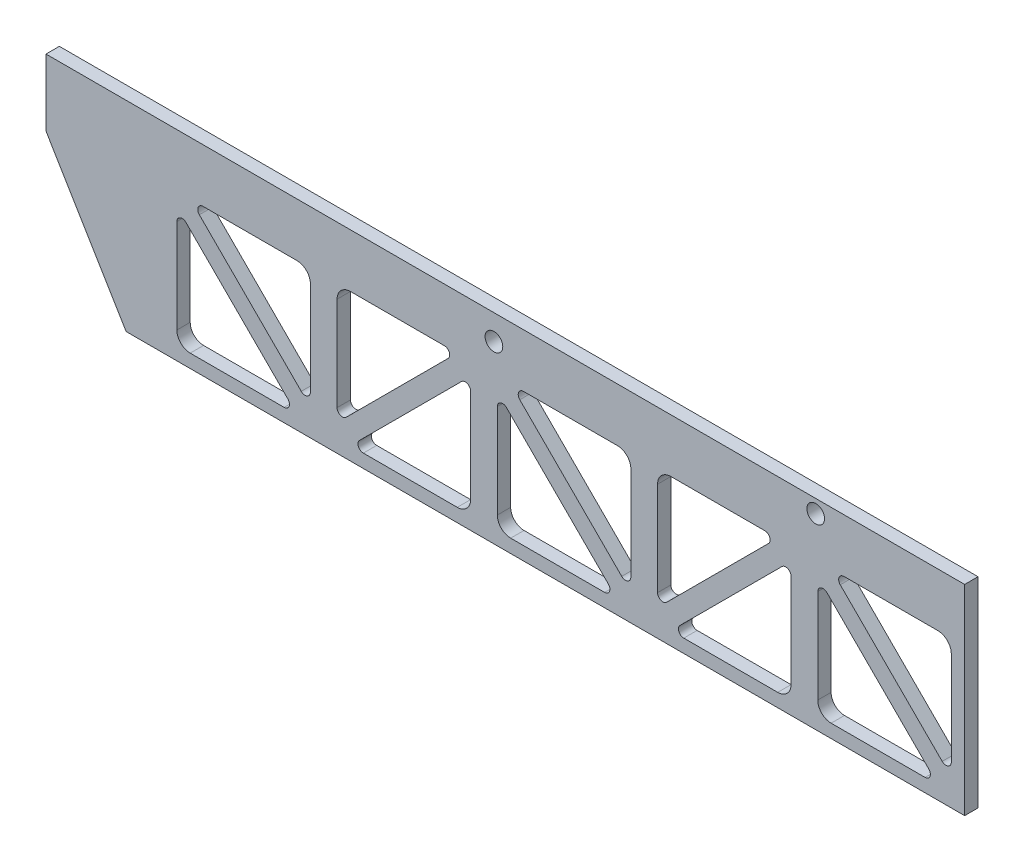
SolidWorks part; units mm, degrees
material "Balsa"
ref_plane "Front Plane" through (0, 0, 0) normal (0, 0, 1) x (1, 0, 0)
ref_plane "Top Plane" through (0, 0, 0) normal (0, 1, 0) x (1, 0, 0)
ref_plane "Right Plane" through (0, 0, 0) normal (1, 0, 0) x (0, 0, -1)
sketch "Model" plane through (0, 0, 0) normal (0, 0, 1) x (1, 0, 0)
  line L0 (-74.8917, 84.8995) -> (-66.8907, 84.8995)
  line L1 (-74.8917, 92.9005) -> (-74.8917, 84.8995)
  line L2 (-66.8907, 92.9005) -> (-74.8917, 92.9005)
  line L3 (-66.8907, 84.8995) -> (-66.8907, 92.9005)
  line L4 (-227.7984, 79.375) -> (-219.7978, 79.375)
  line L5 (-227.7984, 87.3756) -> (-227.7984, 79.375)
  line L6 (-219.7978, 87.3756) -> (-227.7984, 87.3756)
  line L7 (-219.7978, 79.375) -> (-219.7978, 87.3756)
  line L8 (-171.2321, 6.35) -> (-215.9, 6.35)
  line L9 (-222.25, 57.3679) -> (-222.25, 12.7)
  line L10 (-217.9139, 59.1639) -> (-169.4361, 10.6861)
  line L11 (-234.95, 57.3679) -> (-234.95, 12.7)
  line L12 (-241.3, 6.35) -> (-285.9679, 6.35)
  line L13 (-239.2861, 59.1639) -> (-287.7639, 10.6861)
  line L14 (-294.1139, 17.0361) -> (-245.6361, 65.5139)
  line L15 (-298.45, 63.5) -> (-298.45, 18.8321)
  line L16 (-247.4321, 69.85) -> (-292.1, 69.85)
  line L17 (-323.6321, 6.35) -> (-368.3, 6.35)
  line L18 (-374.65, 57.3679) -> (-374.65, 12.7)
  line L19 (-370.3139, 59.1639) -> (-321.8361, 10.6861)
  line L20 (-18.8321, 6.35) -> (-63.5, 6.35)
  line L21 (-69.85, 57.3679) -> (-69.85, 12.7)
  line L22 (-17.0361, 10.6861) -> (-65.5139, 59.1639)
  line L23 (-82.55, 57.3679) -> (-82.55, 12.7)
  line L24 (-88.9, 6.35) -> (-133.5679, 6.35)
  line L25 (-86.8861, 59.1639) -> (-135.3639, 10.6861)
  line L26 (-93.2361, 65.5139) -> (-141.7139, 17.0361)
  line L27 (-146.05, 63.5) -> (-146.05, 18.8321)
  line L28 (-95.0321, 69.85) -> (-139.7, 69.85)
  line L29 (-163.0861, 17.0361) -> (-211.5639, 65.5139)
  line L30 (-165.1, 69.85) -> (-209.7679, 69.85)
  line L31 (-158.75, 63.5) -> (-158.75, 18.8321)
  line L32 (-315.4861, 17.0361) -> (-363.9639, 65.5139)
  line L33 (-317.5, 69.85) -> (-362.1679, 69.85)
  line L34 (-311.15, 63.5) -> (-311.15, 18.8321)
  line L35 (-398.78, 0) -> (-436.88, 63.5)
  line L36 (0, 0) -> (-398.78, 0)
  line L37 (0, 0) -> (0, 95.25)
  line L38 (0, 95.25) -> (-436.88, 95.25)
  line L39 (-436.88, 63.5) -> (-436.88, 95.25)
  line L40 (-6.35, 63.5) -> (-6.35, 18.8321)
  line L41 (-59.1639, 65.5139) -> (-10.6861, 17.0361)
  line L42 (-12.7, 69.85) -> (-57.3679, 69.85)
  arc A0 (-222.25, 12.7) -> (-215.9, 6.35) centre (-215.9, 12.7) ccw
  arc A1 (-217.9139, 59.1639) -> (-222.25, 57.3679) centre (-219.71, 57.3679) ccw
  arc A2 (-171.2321, 6.35) -> (-169.4361, 10.6861) centre (-171.2321, 8.89) ccw
  arc A3 (-234.95, 57.3679) -> (-239.2861, 59.1639) centre (-237.49, 57.3679) ccw
  arc A4 (-241.3, 6.35) -> (-234.95, 12.7) centre (-241.3, 12.7) ccw
  arc A5 (-287.7639, 10.6861) -> (-285.9679, 6.35) centre (-285.9679, 8.89) ccw
  arc A6 (-245.6361, 65.5139) -> (-247.4321, 69.85) centre (-247.4321, 67.31) ccw
  arc A7 (-298.45, 18.8321) -> (-294.1139, 17.0361) centre (-295.91, 18.8321) ccw
  arc A8 (-292.1, 69.85) -> (-298.45, 63.5) centre (-292.1, 63.5) ccw
  arc A9 (-323.6321, 6.35) -> (-321.8361, 10.6861) centre (-323.6321, 8.89) ccw
  arc A10 (-374.65, 12.7) -> (-368.3, 6.35) centre (-368.3, 12.7) ccw
  arc A11 (-370.3139, 59.1639) -> (-374.65, 57.3679) centre (-372.11, 57.3679) ccw
  arc A12 (-69.85, 12.7) -> (-63.5, 6.35) centre (-63.5, 12.7) ccw
  arc A13 (-65.5139, 59.1639) -> (-69.85, 57.3679) centre (-67.31, 57.3679) ccw
  arc A14 (-18.8321, 6.35) -> (-17.0361, 10.6861) centre (-18.8321, 8.89) ccw
  arc A15 (-82.55, 57.3679) -> (-86.8861, 59.1639) centre (-85.09, 57.3679) ccw
  arc A16 (-88.9, 6.35) -> (-82.55, 12.7) centre (-88.9, 12.7) ccw
  arc A17 (-135.3639, 10.6861) -> (-133.5679, 6.35) centre (-133.5679, 8.89) ccw
  arc A18 (-93.2361, 65.5139) -> (-95.0321, 69.85) centre (-95.0321, 67.31) ccw
  arc A19 (-146.05, 18.8321) -> (-141.7139, 17.0361) centre (-143.51, 18.8321) ccw
  arc A20 (-139.7, 69.85) -> (-146.05, 63.5) centre (-139.7, 63.5) ccw
  arc A21 (-163.0861, 17.0361) -> (-158.75, 18.8321) centre (-161.29, 18.8321) ccw
  arc A22 (-209.7679, 69.85) -> (-211.5639, 65.5139) centre (-209.7679, 67.31) ccw
  arc A23 (-158.75, 63.5) -> (-165.1, 69.85) centre (-165.1, 63.5) ccw
  arc A24 (-362.1679, 69.85) -> (-363.9639, 65.5139) centre (-362.1679, 67.31) ccw
  arc A25 (-311.15, 63.5) -> (-317.5, 69.85) centre (-317.5, 63.5) ccw
  arc A26 (-315.4861, 17.0361) -> (-311.15, 18.8321) centre (-313.69, 18.8321) ccw
  arc A27 (-10.6861, 17.0361) -> (-6.35, 18.8321) centre (-8.89, 18.8321) ccw
  arc A28 (-57.3679, 69.85) -> (-59.1639, 65.5139) centre (-57.3679, 67.31) ccw
  arc A29 (-6.35, 63.5) -> (-12.7, 69.85) centre (-12.7, 63.5) ccw
  point P103 (-223.7981, 83.3753)
  point P104 (-223.7981, 87.3756)
  point P105 (-219.7978, 83.3753)
  point P106 (-70.8912, 92.9005)
  point P107 (-66.8907, 88.9)
  point P109 (-70.8912, 88.9)
  dimension "D1" = 95.25
  dimension "D2" = 8.0006
  dimension "D3" = 153.0067
  dimension "D4" = 79.375
extrude "Boss-Extrude1" add sketch "Model" along normal blind 6.35
sketch "Sketch1" plane through (0, 0, 6.35) normal (0, 0, 1) x (1, 0, 0)
  line L0 (-219.7978, 87.3756) -> (-227.7984, 87.3756) construction
  line L1 (-228.0655, 87.5153) -> (-219.6581, 87.5153)
  line L2 (-228.0655, 87.5153) -> (-228.0655, 79.1079)
  line L3 (-228.0655, 79.1079) -> (-219.6581, 79.1079)
  line L4 (-219.6581, 87.5153) -> (-219.6581, 79.1079)
  line L5 (-219.7978, 79.375) -> (-219.7978, 87.3756) construction
  line L6 (-74.8917, 92.9005) -> (-74.8917, 84.8995) construction
  line L7 (-75.0314, 93.1672) -> (-66.624, 93.1672)
  line L8 (-75.0314, 93.1672) -> (-75.0314, 84.7598)
  line L9 (-75.0314, 84.7598) -> (-66.624, 84.7598)
  line L10 (-66.624, 93.1672) -> (-66.624, 84.7598)
  line L11 (-74.8917, 84.8995) -> (-66.8907, 84.8995) construction
  circle A0 centre (-223.8618, 83.3116) radius 4.2037
  circle A1 centre (-70.8277, 88.9635) radius 4.2037
  dimension "D2" = 8.4074
  dimension "D6" = 8.4074
  dimension "D1" = 4.064
  dimension "D3" = 4.064
  dimension "D4" = 4.064
  dimension "D5" = 4.064
extrude "Boss-Extrude2" add sketch "Sketch1" against normal up to surface (6.35 mm away) contours A0 L1 L2 | A0 L4 L1 | A0 L3 L4 | A0 L2 L3 | A1 L7 L8 | A1 L10 L7 | A1 L9 L10 | A1 L8 L9 region at (-227.1266, 86.5763, 6.35) region at (-220.5971, 86.5763, 6.35) region at (-227.1266, 80.0468, 6.35) region at (-220.5971, 80.0468, 6.35) region at (-74.0924, 92.2282, 6.35) region at (-67.563, 92.2282, 6.35) region at (-74.0924, 85.6988, 6.35) region at (-67.563, 85.6988, 6.35) up to face at (-254.508, 50.8, 0)
extrude "Cut-Extrude1" cut sketch "Sketch1<3>" against normal up to surface (6.35 mm away) contours A0 | A1 | A1 region at (-223.8618, 83.3116, 6.35) region at (-70.8277, 88.9635, 6.35) up to face at (-70.8806, 88.9106, 0)
sketch "Sketch1<3>" plane through (0, 0, 6.35) normal (0, 0, 1) x (1, 0, 0) same geometry as "Sketch1"
equation "\"thick\"=0.25"
equation "\"D1@Boss-Extrude1\"=\"thick\""
